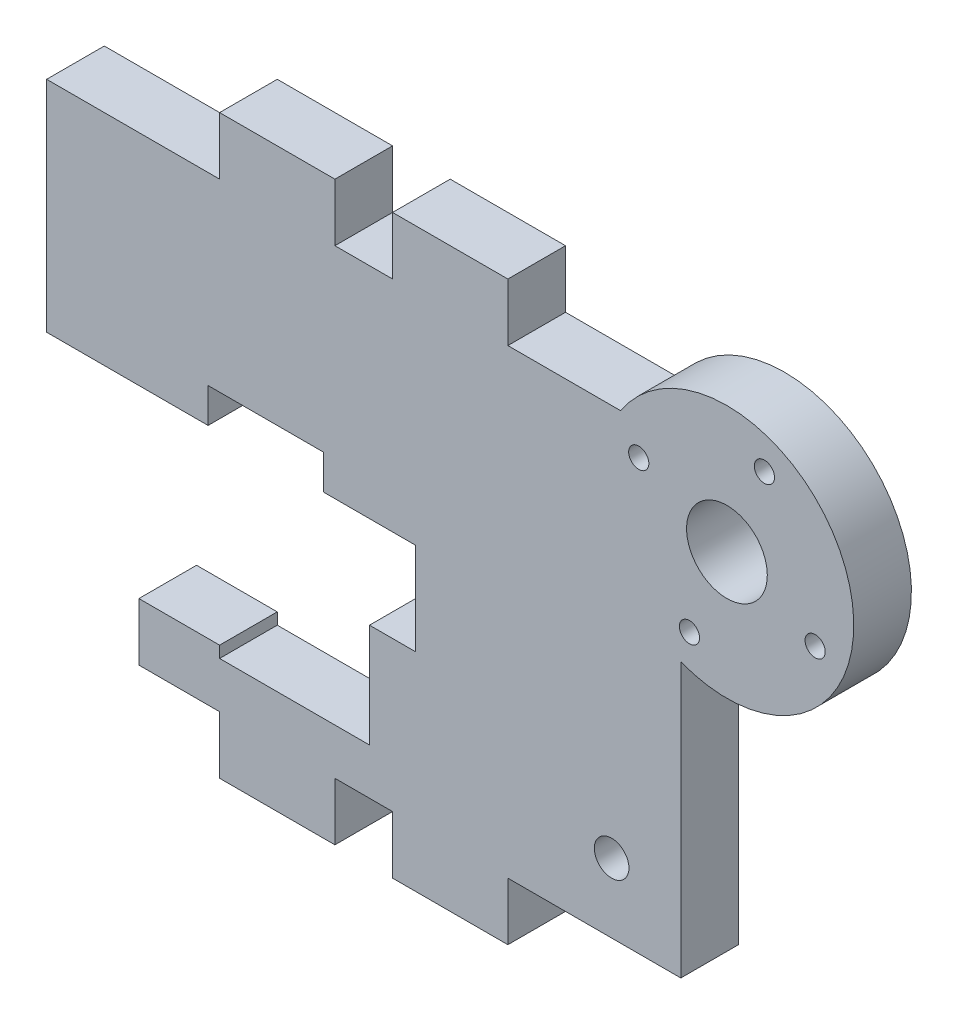
SolidWorks part; units mm, degrees
ref_plane "Plan de face" through (0, 0, 0) normal (0, 0, 1) x (1, 0, 0)
ref_plane "Plan de dessus" through (0, 0, 0) normal (0, 1, 0) x (1, 0, 0)
ref_plane "Plan de droite" through (0, 0, 0) normal (1, 0, 0) x (0, 0, -1)
sketch "Esquisse1" plane through (0, 0, 0) normal (0, 0, 1) x (1, 0, 0)
  line L0 (-1, 20) -> (50, 20) construction
  line L1 (10, 0) -> (15, 0)
  line L2 (0, 5) -> (0, 4)
  line L3 (10, 40) -> (15, 40)
  line L5 (25, 40) -> (34.7805, 40)
  line L6 (0, 40) -> (0, 45)
  line L7 (0, 45) -> (10, 45)
  line L8 (10, 40) -> (10, 45)
  line L9 (25, 0) -> (40, 0)
  line L10 (15, 40) -> (15, 45)
  line L11 (15, 45) -> (25, 45)
  line L12 (25, 40) -> (25, 45)
  line L13 (25, 0) -> (25, -5)
  line L14 (15, -5) -> (25, -5)
  line L15 (15, 0) -> (15, -5)
  line L16 (10, 0) -> (10, -5)
  line L17 (0, -5) -> (10, -5)
  line L18 (0, 0) -> (0, -5)
  line L19 (-1, 20) -> (-1, 24)
  line L20 (0, 4) -> (13, 4)
  line L21 (44, 34) -> (36.35, 34) construction
  line L22 (-1, 24) -> (9, 24)
  line L23 (17, 13) -> (17, 21)
  line L24 (0, 0) -> (-7, 0)
  line L25 (0, 0) -> (0, 5)
  line L26 (0, 5) -> (-7, 5)
  line L27 (-7, 0) -> (-7, 5)
  line L28 (0, 40) -> (-15, 40)
  line L29 (0, 40) -> (0, 21)
  line L30 (0, 21) -> (-15, 21)
  line L31 (-15, 40) -> (-15, 21)
  line L32 (17, 21) -> (9, 21)
  line L33 (36.35, 34) -> (36.35, 37.25) construction
  line L35 (9, 21) -> (9, 24)
  line L36 (17, 13) -> (13, 13)
  line L38 (40, 0) -> (40, 23.753)
  line L39 (13, 13) -> (13, 4)
  circle A0 centre (34, 6) radius 1.5
  circle A1 centre (44, 34) radius 3.5
  arc A2 (40, 23.753) -> (34.7805, 40) centre (44, 34) ccw
  circle A3 centre (36.35, 34) radius 0.875 construction
  circle A4 centre (36.35, 37.25) radius 0.875
  circle A5 centre (47.25, 41.65) radius 0.875
  circle A6 centre (51.65, 30.75) radius 0.875
  circle A7 centre (40.75, 26.35) radius 0.875
  point P56 (44, 34)
  dimension "D18" = 15
  dimension "D19" = 3
  dimension "D25" = 3.25
  dimension "D27" = 11
  dimension "D28" = 1.75
  dimension "D24" = 7
  dimension "D1" = 40
  dimension "D3" = 10
  dimension "D4" = 5
  dimension "D5" = 5
  dimension "D6" = 5
  dimension "D7" = 7
  dimension "D8" = 15
  dimension "D9" = 19
  dimension "D10" = 10
  dimension "D11" = 4
  dimension "D12" = 4
  dimension "D13" = 4
  dimension "D14" = 3
  dimension "D15" = 8
  dimension "D16" = 4
  dimension "D17" = 8
  dimension "D20" = 6
  dimension "D21" = 6
  dimension "D22" = 23
  dimension "D23" = 6
  dimension "D26" = 7.65
  dimension "D29" = 4
extrude "Boss.-Extru.1" add sketch "Esquisse1" along normal blind 5 contours L29 L0 L5 L12 L11 L10 L3 L8 L7 L6 | L28 L31 L30 L29 | L0 L19 L22 L23 L20 L2 L25 L18 L17 L16 L1 L15 L14 L13 L9 | L27 L24 L25 L26 region at (24.7853, 23.0022, 0) region at (-3.5, 2.5, 0) region at (-7.5745, 30.5851, 0)
